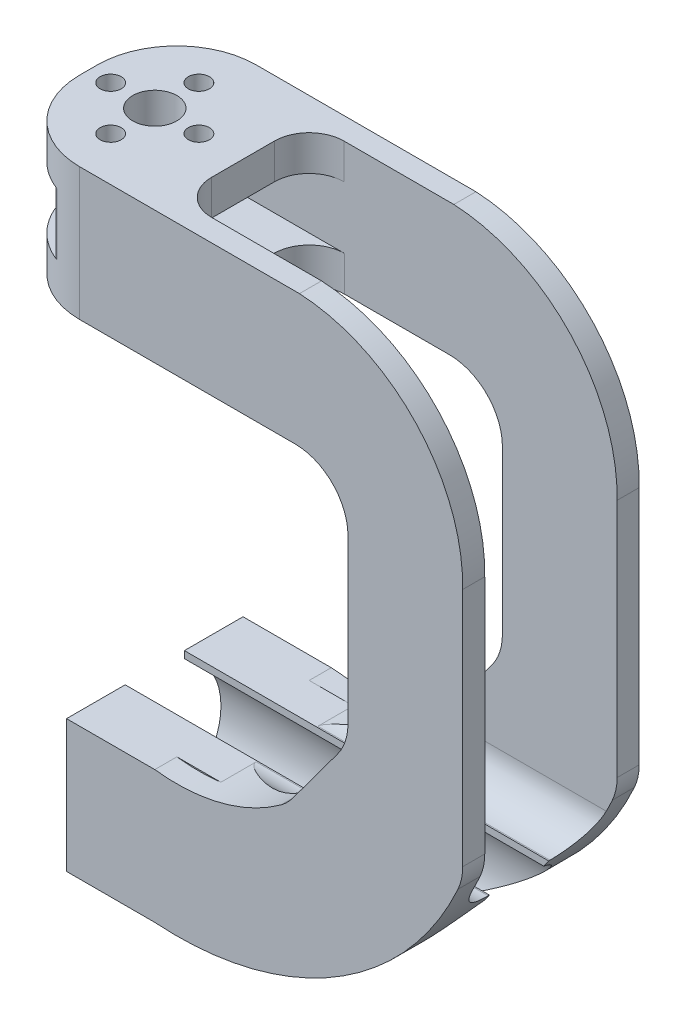
SolidWorks part; units mm, degrees
ref_plane "Front Plane" through (0, 0, 0) normal (0, 0, 1) x (1, 0, 0)
ref_plane "Top Plane" through (0, 0, 0) normal (0, 1, 0) x (1, 0, 0)
ref_plane "Right Plane" through (0, 0, 0) normal (1, 0, 0) x (0, 0, -1)
sketch "Sketch1" plane through (0, 0, 0) normal (0, 0, 1) x (1, 0, 0)
  line L0 (0, 0) -> (0, -38.1)
  line L2 (6.3321, 139.4742) -> (-44.4679, 139.4742)
  line L3 (-44.4679, 139.4742) -> (-44.4679, 101.3742)
  line L4 (-44.4679, 101.3742) -> (22.1557, 101.3742)
  line L8 (6.3321, 139.4742) -> (41.641, 139.4742)
  line L10 (88.6314, 89.208) -> (88.6314, 20.0971)
  line L14 (22.1557, 101.3742) -> (40.3714, 101.3742)
  line L15 (55.6114, 86.1342) -> (55.6114, 39.2601)
  line L17 (39.642, 12.647) -> (52.6238, 30.1971)
  arc A0 (0, -38.1) -> (87.2657, 13.7915) centre (6.3321, 50.5742) ccw
  arc A2 (0, 0) -> (36.3716, 9.398) centre (6.3321, 50.5742) ccw
  arc A9 (88.6314, 20.0971) -> (87.2657, 13.7915) centre (73.3914, 20.0971) cw
  arc A10 (40.3714, 101.3742) -> (55.6114, 86.1342) centre (40.3714, 86.1342) cw
  arc A11 (52.6238, 30.1971) -> (55.6114, 39.2601) centre (40.3714, 39.2601) ccw
  arc A12 (39.642, 12.647) -> (36.3716, 9.398) centre (27.3897, 21.7099) cw
  arc A13 (88.6314, 89.208) -> (41.641, 139.4742) centre (39.1101, 90.0111) ccw
  point P13 (0, 0)
  point P17 (0, 0)
  dimension "D2" = 88.9
  dimension "D4" = 15.24
  dimension "D6" = 33.02
  dimension "D7" = 15.24
  dimension "D8" = 15.24
  dimension "D9" = 15.24
  dimension "D1" = 50.8
  dimension "D3" = 38.1
  dimension "D10" = 38.1
extrude "Boss-Extrude1" add sketch "Sketch1" along normal blind 6.35
sketch "Sketch2" plane through (0, 0, 0) normal (-1, 0, 0) x (0, 0, 1)
  line L0 (6.35, 0) -> (6.35, -38.1) construction
  line L1 (6.35, -38.1) -> (16.8761, -38.1)
  line L2 (16.8761, -38.1) -> (16.8761, -36.0866)
  line L3 (25.4, -19.05) -> (-24.6813, -19.05) construction
  line L4 (6.35, 0) -> (6.35, -38.1)
  line L5 (16.8761, 0) -> (16.8761, -2.0134)
  line L6 (6.35, 0) -> (16.8761, 0)
  arc A0 (16.8761, -2.0134) -> (16.8761, -36.0866) centre (25.4, -19.05) ccw
  point P2 (6.35, -19.05)
  point P14 (6.35, -19.05)
  line M8 (6.35, -38.1) -> (6.35, 0)
  dimension "D2" = 38.1
  dimension "D1" = 19.05
extrude "Boss-Extrude2" add sketch "Sketch2" against normal up to surface (61.6104 mm away) contours A0 L5 L6 L4 | A0 L1 L2 M8 region at (0, -33.5618, 9.9567) region at (0, -4.5382, 9.9567) up to face at (47.701, -18.9957, 3.175)
sketch "Sketch3" plane through (0, 0, 0) normal (-1, 0, 0) x (0, 0, 1)
  line L0 (6.35, -38.1) -> (0, -38.1) construction
  line L1 (0, 0) -> (0, -38.1) construction
  line L3 (6.35, 0) -> (16.8761, 0) construction
  circle A0 centre (6.35, -31.75) radius 3.2639
  circle A1 centre (6.35, -6.35) radius 3.2639
  dimension "D1" = 6.5278
  dimension "D2" = 6.35
  dimension "D3" = 6.35
  dimension "D4" = 6.35
extrude "Cut-Extrude1" cut sketch "Sketch3" against normal blind 12.7 contours A0 | A1 region at (0, -31.75, 6.35)
fillet "Fillet1" radius 10.16 1 edges at (46.0546, 0, 6.35)
sketch "Sketch6" plane through (0, 0, 0) normal (-1, 0, 0) x (0, 0, 1)
  line L6 (6.35, 0) -> (0, 0)
  line L7 (6.35, 0) -> (0, 0)
  line L9 (6.35, -38.1) -> (16.8761, -38.1)
  line L10 (6.35, -38.1) -> (16.8761, -38.1)
  line L12 (0, 0) -> (0, -38.1)
  line L13 (0, -38.1) -> (6.35, -38.1)
  line L14 (16.8761, -38.1) -> (16.8761, -36.0866)
  line L15 (16.8761, -2.0134) -> (16.8761, 0)
  line L16 (16.8761, 0) -> (6.35, 0)
  line L18 (0, 0) -> (0, -38.1)
  line L19 (0, -38.1) -> (6.35, -38.1)
  line L20 (16.8761, -38.1) -> (16.8761, -36.0866)
  line L21 (16.8761, -2.0134) -> (16.8761, 0)
  line L22 (16.8761, 0) -> (6.35, 0)
  circle A1 centre (6.35, -6.35) radius 3.2639
  arc A2 (16.8761, -2.0134) -> (16.8761, -36.0866) centre (25.4, -19.05) ccw
  arc A3 (16.8761, -2.0134) -> (16.8761, -36.0866) centre (25.4, -19.05) ccw
  circle A4 centre (6.35, -31.75) radius 3.2639
  circle A5 centre (6.35, -31.75) radius 3.2639 construction
  circle A6 centre (6.35, -6.35) radius 3.2639 construction
  dimension "D1" = 0
extrude "Boss-Extrude3" add sketch "Sketch6" along normal blind 25.4
ref_plane "Plane1" through (0, 0, 25.4) normal (0, 0, 1) x (1, 0, 0)
mirror "Mirror2" about plane through (0, 0, 25.4) normal (0, 0, 1) of bodies 108
sketch "Sketch12" plane through (0, 0, 6.35) normal (0, 0, 1) x (1, 0, 0)
  line L1 (-44.4679, 139.4742) -> (0, 139.4742)
  line L2 (-44.4679, 139.4742) -> (-44.4679, 129.3142)
  line L3 (-44.4679, 129.3142) -> (0, 129.3142)
  line L4 (0, 139.4742) -> (0, 129.3142)
  line L5 (-44.4679, 101.3742) -> (0, 101.3742)
  line L6 (-44.4679, 101.3742) -> (-44.4679, 111.5342)
  line L7 (-44.4679, 111.5342) -> (0, 111.5342)
  line L8 (0, 101.3742) -> (0, 111.5342)
  dimension "D1" = 10.16
  dimension "D2" = 10.16
extrude "Boss-Extrude4" add sketch "Sketch12" along normal up to next
sketch "Sketch13" plane through (0, 139.4742, 0) normal (0, 1, 0) x (1, 0, 0)
  line L0 (-44.4679, -50.8) -> (-44.4679, 0) construction
  circle A0 centre (-25.4, -25.4) radius 6.35
  circle A1 centre (-38.1, -25.4) radius 3.0386
  circle A2 centre (-25.4, -12.7) radius 3.0386
  circle A3 centre (-12.7, -25.4) radius 3.0386
  circle A4 centre (-25.4, -38.1) radius 3.0386
  point P2 (-25.4, 0)
  point P3 (-44.4679, -25.4)
  point P18 (-25.4, -25.4)
  dimension "D1" = 12.7
  dimension "D2" = 12.7
  dimension "D3" = 4
extrude "Cut-Extrude4" cut sketch "Sketch13" against normal up to surface (38.1 mm away) up to face at (9.0687, 101.3742, 25.4)
fillet "Fillet2" radius 10 2 edges at (0, 134.3942, 6.35) (0, 134.3942, 44.45)
fillet "Fillet3" radius 22.86 2 edges at (-44.4679, 120.4242, 50.8) (-44.4679, 120.4242, 0)
fillet "Fillet4" radius 2.54 2 edges at (-37.4192, 120.4242, 6.35) (-37.4192, 120.4242, 44.45)
fillet "Fillet5" radius 10.16 2 edges at (0, 106.4542, 44.45) (0, 106.4542, 6.35)
